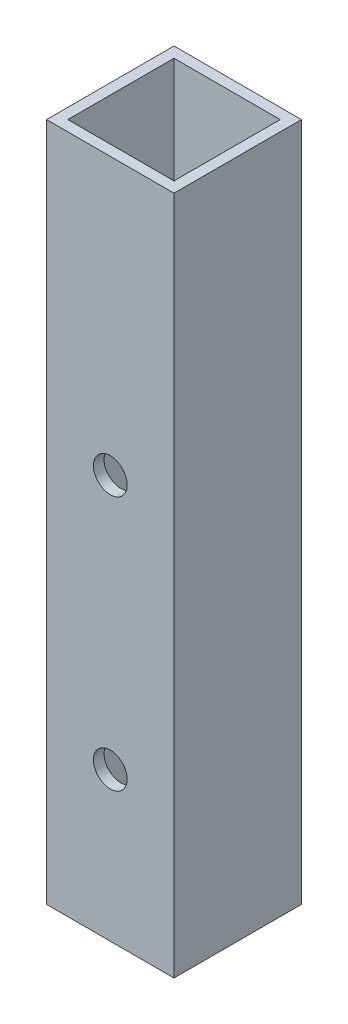
SolidWorks part; units mm, degrees
material "6061-T6 (SS)"
ref_plane "Front Plane" through (0, 0, 0) normal (0, 0, 1) x (1, 0, 0)
ref_plane "Top Plane" through (0, 0, 0) normal (0, 1, 0) x (1, 0, 0)
ref_plane "Right Plane" through (0, 0, 0) normal (1, 0, 0) x (0, 0, -1)
sketch "Sketch1" plane through (0, 0, 0) normal (0, 1, 0) x (1, 0, 0)
  line L0 (0, 19.05) -> (3.175, 19.05) construction
  line L1 (0, 0) -> (38.1, 0)
  line L2 (0, 0) -> (0, 38.1)
  line L3 (0, 38.1) -> (38.1, 38.1)
  line L4 (38.1, 0) -> (38.1, 38.1)
  line L5 (3.175, 3.175) -> (34.925, 3.175)
  line L6 (3.175, 3.175) -> (3.175, 34.925)
  line L7 (3.175, 34.925) -> (34.925, 34.925)
  line L8 (34.925, 3.175) -> (34.925, 34.925)
  line L9 (34.925, 19.05) -> (38.1, 19.05) construction
  line L10 (19.05, 3.175) -> (19.05, 0) construction
  line L11 (19.05, 34.925) -> (19.05, 38.1) construction
  dimension "D1" = 38.1
  dimension "D2" = 38.1
  dimension "D3" = 3.175
extrude "Boss-Extrude1" add sketch "Sketch1" along normal blind 203.2
hole_wizard "X (0.397) Diameter Hole1" positions "Sketch3" profile "Sketch2" hole size "X" standard "ANSI Inch" end condition through all
sketch "Sketch3" plane through (0, 0, 0) normal (0, 0, 1) x (1, 0, 0)
  line L0 (19.05, 0) -> (19.05, 120.65) construction
  line L1 (0, 0) -> (38.1, 0) construction
  line L2 (19.05, 120.65) -> (19.05, 203.2) construction
  line L3 (0, 203.2) -> (38.1, 203.2) construction
  point P0 (19.05, 120.65)
  point P11 (19.05, 44.45)
  dimension "D1" = 120.65
  dimension "D2" = 76.2
sketch "Sketch2" plane through (19.05, 120.65, 0) normal (1, 0, 0) x (0, -1, 0)
  line L0 (0, 0) -> (0, 38.1)
  line L1 (0, 38.1) -> (5.0419, 38.1)
  line L2 (5.0419, 38.1) -> (5.0419, 0)
  line L5 (5.0419, 0) -> (0, 0)
  line L11 (0, -6.35) -> (0, 107.95) construction
  dimension "Thru Hole Dia." = 10.0838
  dimension "Thru Hole Depth" = 38.1
